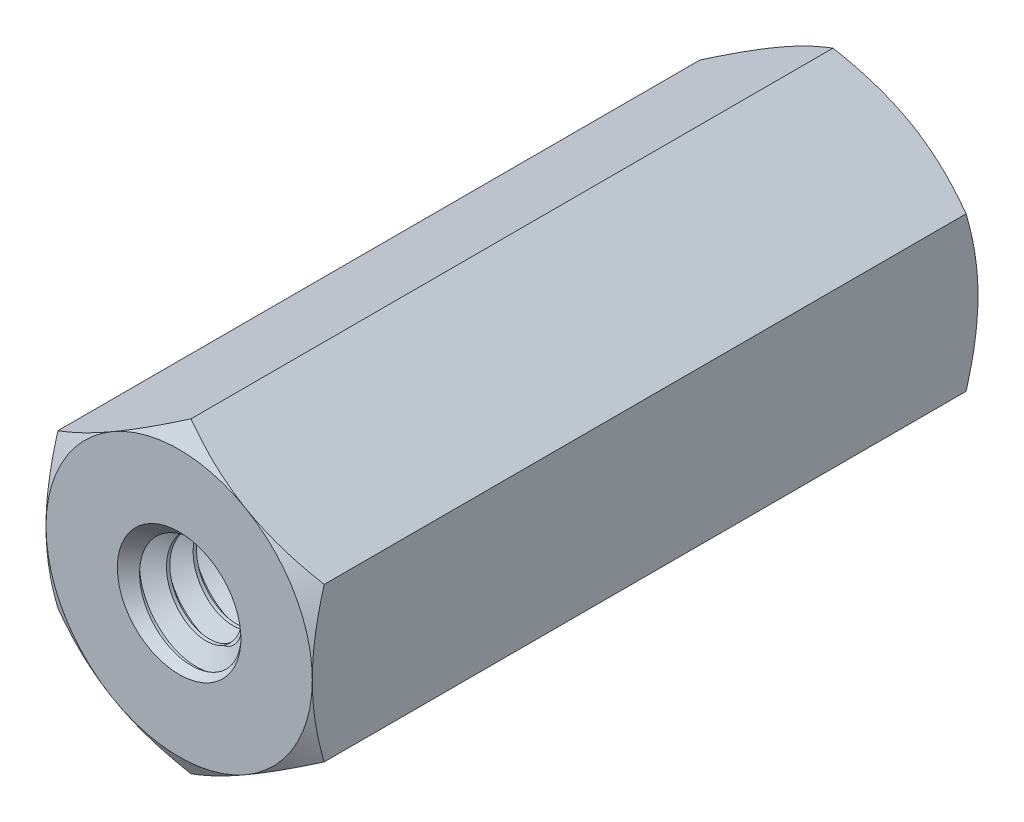
SolidWorks part; units mm, degrees
ref_plane "Front Plane" through (0, 0, 0) normal (0, 0, 1) x (1, 0, 0)
ref_plane "Top Plane" through (0, 0, 0) normal (0, 1, 0) x (1, 0, 0)
ref_plane "Right Plane" through (0, 0, 0) normal (1, 0, 0) x (0, 0, -1)
sketch "Sketch3" plane through (0, 0, 0) normal (1, 0, 0) x (0, 0, -1)
  line L0 (-7.9375, 0) -> (7.9375, 0) construction
  line L1 (0, 3.175) -> (0, -3.175) construction
  line L2 (-7.9375, 1.4224) -> (-7.9375, -1.4224) construction
  point P2 (3.175, 0)
  point P3 (-3.175, 0)
  dimension "D1" = 4.7625
  dimension "Length" = 15.875
  dimension "Min Thread Length" = 4.7625
  dimension "Thread Dia" = 2.8448
  dimension "Hex" = 6.35
sketch "Sketch1" plane through (0, 0, 0) normal (0, 0, 1) x (1, 0, 0)
  line L1 (0, 3.6662) -> (-3.175, 1.8331)
  line L2 (-3.175, 1.8331) -> (-3.175, -1.8331)
  line L3 (-3.175, -1.8331) -> (0, -3.6662)
  line L4 (0, -3.6662) -> (3.175, -1.8331)
  line L5 (3.175, -1.8331) -> (3.175, 1.8331)
  line L6 (3.175, 1.8331) -> (0, 3.6662)
  circle A0 centre (0, 0) radius 3.175 construction
  circle A1 centre (0, 0) radius 1.4224
extrude "Extrude1" add sketch "Sketch1" along normal up to vertex (7.9375 mm away) and the other way up to vertex (7.9375 mm away) up to point (0, 0, 7.9375) other way up to point (0, 0, -7.9375)
sketch "Sketch11" plane through (0, 0, -7.9375) normal (0, 0, -1) x (-1, 0, 0)
  circle A0 centre (0, 0) radius 1.4224 construction
  circle A1 centre (0, 0) radius 1.4224
curve "Helix/Spiral1" pitch 0.635 height 16.51 radius 1.4224 centre (0, 0, -7.9375) axis (0, 0, 1) start towards (0, 1, 0) parameters "Pitch"=0.635
sketch "Sketch12" plane through (0, 0, 0) normal (1, 0, 0) x (0, 0, -1)
  line L0 (8.4931, 1.4224) -> (7.9375, 1.4224)
  line L1 (8.4931, 1.4224) -> (8.255, 1.01)
  line L2 (8.255, 1.01) -> (8.1756, 1.01)
  line L3 (8.1756, 1.01) -> (7.9375, 1.4224)
  line L4 (8.2153, 1.01) -> (8.2153, 1.4224) construction
  line L5 (8.3741, 1.2162) -> (8.0566, 1.2162) construction
  dimension "D1" = 0.0794
  dimension "D2" = 0.3175
  dimension "D3" = 60
sweep "Sweep1" add profiles "Sketch12" path "Helix/Spiral1"
sketch "Sketch6" plane through (0, 0, -7.9375) normal (0, 0, -1) x (-1, 0, 0)
  line L6 (0, 3.6662) -> (-3.175, 1.8331)
  line L7 (-3.175, 1.8331) -> (-3.175, -1.8331)
  line L8 (-3.175, -1.8331) -> (0, -3.6662)
  line L9 (0, -3.6662) -> (3.175, -1.8331)
  line L10 (3.175, -1.8331) -> (3.175, 1.8331)
  line L11 (3.175, 1.8331) -> (0, 3.6662)
  line L12 (0, 3.6662) -> (-3.175, 1.8331)
  line L13 (-3.175, 1.8331) -> (-3.175, -1.8331)
  line L14 (-3.175, -1.8331) -> (0, -3.6662)
  line L15 (0, -3.6662) -> (3.175, -1.8331)
  line L16 (3.175, -1.8331) -> (3.175, 1.8331)
  line L17 (3.175, 1.8331) -> (0, 3.6662)
  dimension "D1" = 0
extrude "Extrude2" cut sketch "Sketch6" along normal through all
sketch "Sketch7" plane through (0, 0, -7.9375) normal (0, 0, -1) x (-1, 0, 0)
  circle A2 centre (0, 0) radius 1.4732
  circle A3 centre (0, 0) radius 1.4732
  dimension "D1" = 0.0508
extrude "Extrude3" cut sketch "Sketch7" against normal through all draft 43
sketch "Sketch8" plane through (0, 0, -7.9375) normal (0, 0, -1) x (-1, 0, 0)
  circle A0 centre (0, 0) radius 3.175 construction
  circle A1 centre (0, 0) radius 3.175
extrude "Extrude4" cut sketch "Sketch8" against normal through all draft 60 flip side to cut
mirror "Mirror1" about plane through (0, 0, 0) normal (0, 0, 1) of "Extrude2", "Extrude3", "Extrude4"
sketch "Sketch9" [suppressed] plane through (0, 0, 0) normal (1, 0, 0) x (0, 0, -1)
  line L1 (-1.5875, 0.8128) -> (1.5875, 0.8128)
  line L2 (-1.5875, 0.8128) -> (-1.5875, 0)
  line L3 (-1.5875, 0) -> (1.5875, 0)
  line L4 (1.5875, 0.8128) -> (1.5875, 0)
  line L7 (-6.35, 0) -> (6.35, 0) construction
revolve "Revolve" [suppressed] add sketch "Sketch9" angle 360 about L0
sketch "Sketch10" [suppressed] plane through (0, 0, 0) normal (1, 0, 0) x (0, 0, -1)
  line L0 (6.35, 0.762) -> (1.5875, 0.762)
  line L1 (-6.35, 0.762) -> (-1.5875, 0.762)
  line L2 (1.5875, 0.762) -> (1.5875, -0.762)
  line L3 (-6.35, -0.8128) -> (-1.5875, -0.8128)
  line L4 (-1.5875, 0.762) -> (-1.5875, -0.8128)
  line L5 (1.5875, -0.762) -> (6.35, -0.762)
equation "\"D1@Sketch3\" = \"Min Thread Length@Sketch3\""
equation "\"D3@Helix/Spiral1\" = \"Length@Sketch3\"+\"Pitch@Helix/Spiral1\""
equation "\"D1@Sketch12\" = \"Pitch@Helix/Spiral1\"*.125"
equation "\"D2@Sketch12\" = \"Pitch@Helix/Spiral1\"*.5"
